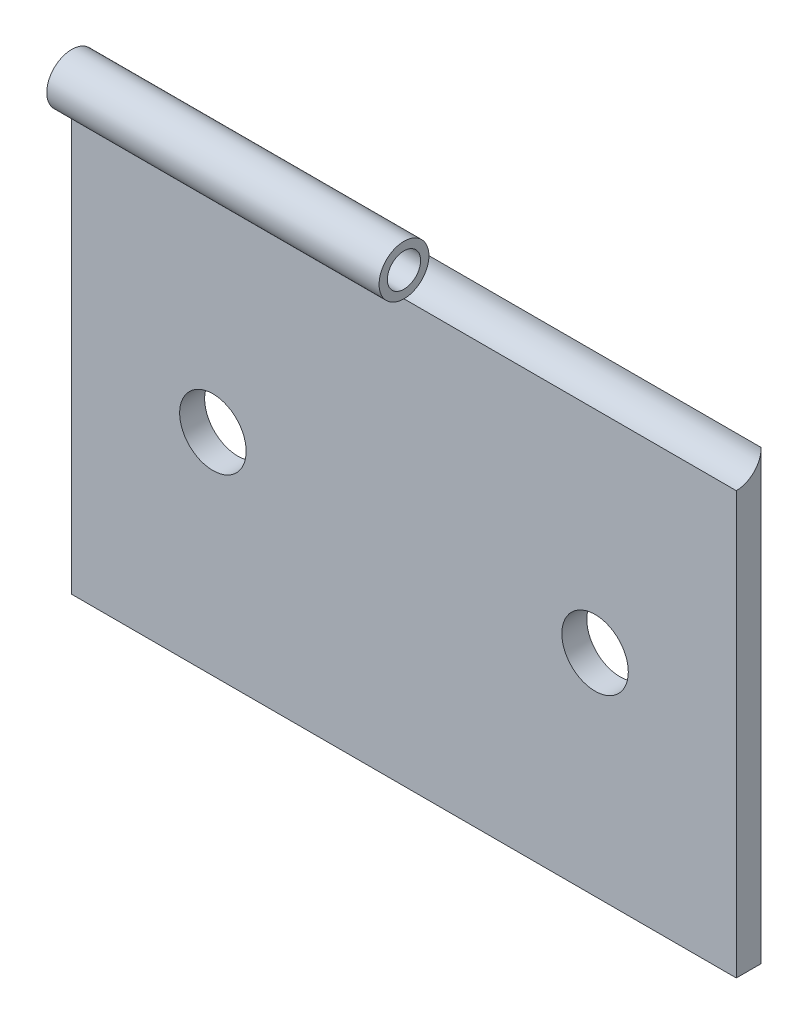
SolidWorks part; units mm, degrees
material "AISI 316 Chapa de acero inoxidable (SS)"
ref_plane "Alzado" through (0, 0, 0) normal (0, 0, 1) x (1, 0, 0)
ref_plane "Planta" through (0, 0, 0) normal (0, 1, 0) x (1, 0, 0)
ref_plane "Vista lateral" through (0, 0, 0) normal (1, 0, 0) x (0, 0, -1)
sketch "Croquis1" plane through (0, 0, 0) normal (1, 0, 0) x (0, 0, -1)
  line L0 (0, 14.554) -> (0, 0) construction
  line L1 (-0.75, -12.7) -> (0.75, -12.7)
  line L2 (-0.75, -12.7) -> (-0.75, 12.7)
  line L4 (0.75, -12.7) -> (0.75, 12.7)
  line L5 (-0.75, -12.7) -> (0.75, 12.7) construction
  line L6 (-0.75, 12.7) -> (0.75, -12.7) construction
  line L7 (-0.75, 12.7) -> (-0.75, 14.2) construction
  line L8 (0.75, 12.7) -> (0.75, 14.2)
  arc A2 (0.75, 14.2) -> (-0.75, 12.7) centre (-0.75, 14.2) ccw
  circle A3 centre (-0.75, 14.2) radius 1
  point P0 (0, 0)
  dimension "D3" = 2
  dimension "D1" = 25.4
  dimension "D2" = 1.5
extrude "Saliente-Extruir1" add sketch "Croquis1" along normal blind 20 and the other way blind 20
sketch "Croquis3" plane through (20, 0, 0) normal (1, 0, 0) x (0, 0, -1)
  circle A0 centre (-0.75, 14.2) radius 1.5
extrude "Cortar-Extruir1" cut sketch "Croquis3" against normal blind 20
sketch "Croquis4" plane through (0, 0, 0.75) normal (0, 0, 1) x (1, 0, 0)
  line L0 (11.5, 0) -> (-11.5, 0)
  circle A0 centre (-11.5, 0) radius 2
  circle A1 centre (11.5, 0) radius 2
  point P4 (0, 0)
  dimension "D2" = 4
  dimension "D1" = 23
extrude "Cortar-Extruir2" cut sketch "Croquis4" against normal up to surface (1.5 mm away) contours A0 | A1 region at (-13.4434, 0, 0.75) region at (11.5, 1.9434, 0.75) up to face at (0, 3.44, -0.75)
sketch "Croquis5" plane through (0, 0, -0.75) normal (0, 0, -1) x (-1, 0, 0)
  line L0 (0, 12.7) -> (-20, 12.7) construction
  line L1 (20, 12.7) -> (0, 12.7) construction
  line L2 (0, 12.7) -> (-20, 12.7)
  line L3 (20, 12.7) -> (0, 12.7)
  line L4 (0, 12.7) -> (0, -12.7) construction
  line L5 (20, -12.7) -> (-20, -12.7) construction
  line L6 (-10, 12.7) -> (-10, -12.7)
  line L7 (10, 12.7) -> (10, -12.7)
  line L8 (-20, 12.7) -> (-20, 10.7)
  line L9 (-20, -12.7) -> (-20, 14.2) construction
  line L10 (-20, 10.7) -> (-10, 7.0603)
  line L11 (20, 10.7) -> (10, 7.0603)
  line L12 (20, 12.7) -> (20, 10.7)
  line L18 (20, 14.2) -> (0, 14.2)
  line L19 (0, 14.2) -> (-20, 14.2)
  line L20 (-20, 14.2) -> (-20, -12.7)
  line L21 (-20, -12.7) -> (20, -12.7)
  line L22 (20, -12.7) -> (20, 14.2)
  line L23 (20, 14.2) -> (0, 14.2)
  line L24 (0, 14.2) -> (-20, 14.2)
  line L25 (-20, 14.2) -> (-20, -12.7)
  line L26 (-20, -12.7) -> (20, -12.7)
  line L27 (20, -12.7) -> (20, 14.2)
  dimension "D3" = 110
  dimension "D4" = 2
  dimension "D1" = 10
  dimension "D2" = 10
  dimension "D5" = 0
